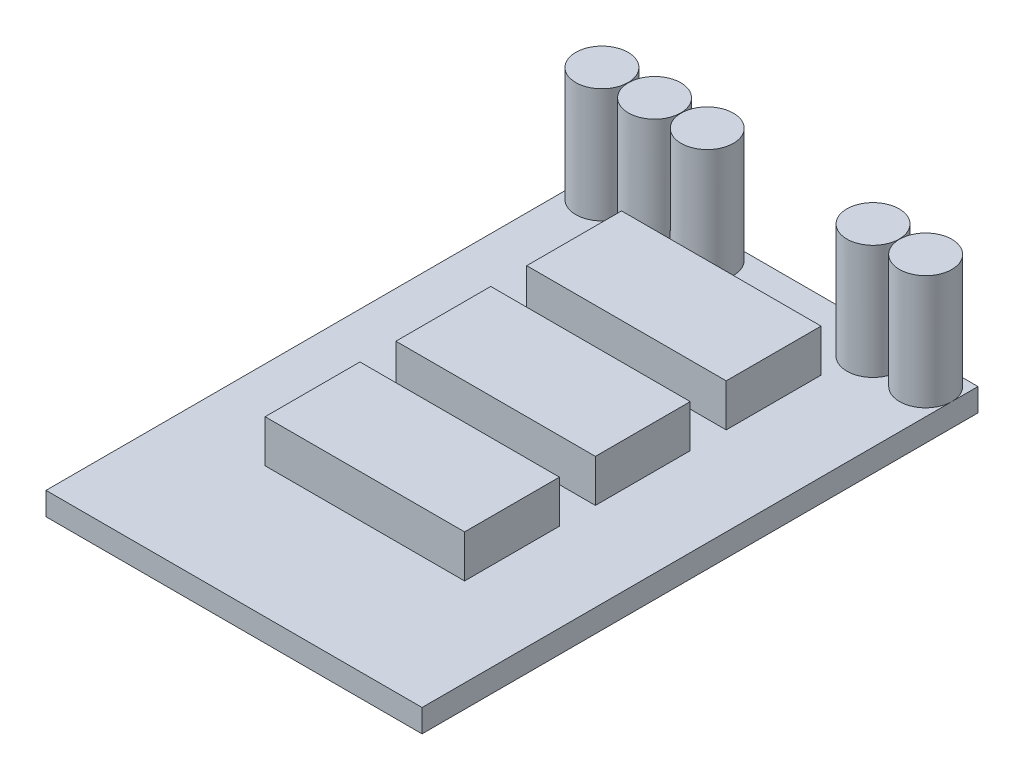
SolidWorks part; units mm, degrees
ref_plane "Спереди" through (0, 0, 0) normal (0, 0, 1) x (1, 0, 0)
ref_plane "Сверху" through (0, 0, 0) normal (0, 1, 0) x (1, 0, 0)
ref_plane "Справа" through (0, 0, 0) normal (1, 0, 0) x (0, 0, -1)
other "Configuration Table"
sketch "Sketch1" plane through (0, 0, 0) normal (0, 1, 0) x (1, 0, 0)
  line L1 (-57.5, 85) -> (57.5, 85)
  line L2 (-57.5, 85) -> (-57.5, -85)
  line L3 (-57.5, -85) -> (57.5, -85)
  line L4 (57.5, 85) -> (57.5, -85)
  line L5 (-57.5, 85) -> (57.5, -85) construction
  line L6 (-57.5, -85) -> (57.5, 85) construction
  point P0 (0, 0)
  dimension "D1" = 115
  dimension "D2" = 170
extrude "Boss-Extrude1" add sketch "Sketch1" along normal blind 7
sketch "Sketch2" plane through (0, 7, 0) normal (0, 1, 0) x (1, 0, 0)
  line L0 (57.5, 85) -> (-57.5, 85) construction
  line L1 (-57.5, 85) -> (-57.5, -85) construction
  line L2 (57.5, -85) -> (57.5, 85) construction
  line L3 (0, 93.731) -> (0, -92.3795) construction
  line L4 (-30.5, 64) -> (30.5, 64)
  line L5 (-30.5, 64) -> (-30.5, 35)
  line L6 (-30.5, 35) -> (30.5, 35)
  line L7 (30.5, 64) -> (30.5, 35)
  line L8 (-30.5, 24) -> (30.5, 24)
  line L9 (-30.5, 24) -> (-30.5, -5)
  line L10 (-30.5, -5) -> (30.5, -5)
  line L11 (30.5, 24) -> (30.5, -5)
  line L12 (-30.5, -16) -> (30.5, -16)
  line L13 (-30.5, -16) -> (-30.5, -45)
  line L14 (-30.5, -45) -> (30.5, -45)
  line L15 (30.5, -16) -> (30.5, -45)
  circle A0 centre (-49.5, 77) radius 8
  circle A1 centre (-33.4, 77) radius 8
  circle A2 centre (-17.3, 77) radius 8
  circle A3 centre (33.4, 77) radius 8
  circle A4 centre (49.5, 77) radius 8
  dimension "D1" = 16
  dimension "D2" = 61
  dimension "D3" = 29
  dimension "D4" = 5
  dimension "D5" = 11
  dimension "D6" = 11
  dimension "D7" = 0.1
  dimension "D8" = 0.1
  dimension "D9" = 0.1
extrude "Boss-Extrude6" add sketch "Sketch2" along normal blind 13 contours L3 L4 L5 L6 | L4 L3 L6 L7 | L8 L3 L10 L11 | L3 L8 L9 L10 | L3 L12 L13 L14 | L12 L3 L14 L15 region at (15.25, 7, -49.5) region at (-15.25, 7, -49.5) region at (15.25, 7, 30.5) region at (-15.25, 7, 30.5) region at (15.25, 7, -9.5) region at (-15.25, 7, -9.5)
extrude "Boss-Extrude9" add sketch "Sketch2<6>" along normal blind 35 contours A0 | A1 | A2 | A3 | A4 region at (-49.5, 7, -77) region at (-33.4, 7, -77) region at (-17.3, 7, -77) region at (33.4, 7, -77) region at (49.5, 7, -77)
sketch "Sketch2<6>" plane through (0, 7, 0) normal (0, 1, 0) x (1, 0, 0) same geometry as "Sketch2"
equation "\"D6@Sketch2\"=\"D5@Sketch2\""
equation "\"D8@Sketch2\"=\"D7@Sketch2\""
equation "\"D9@Sketch2\"=\"D7@Sketch2\""
